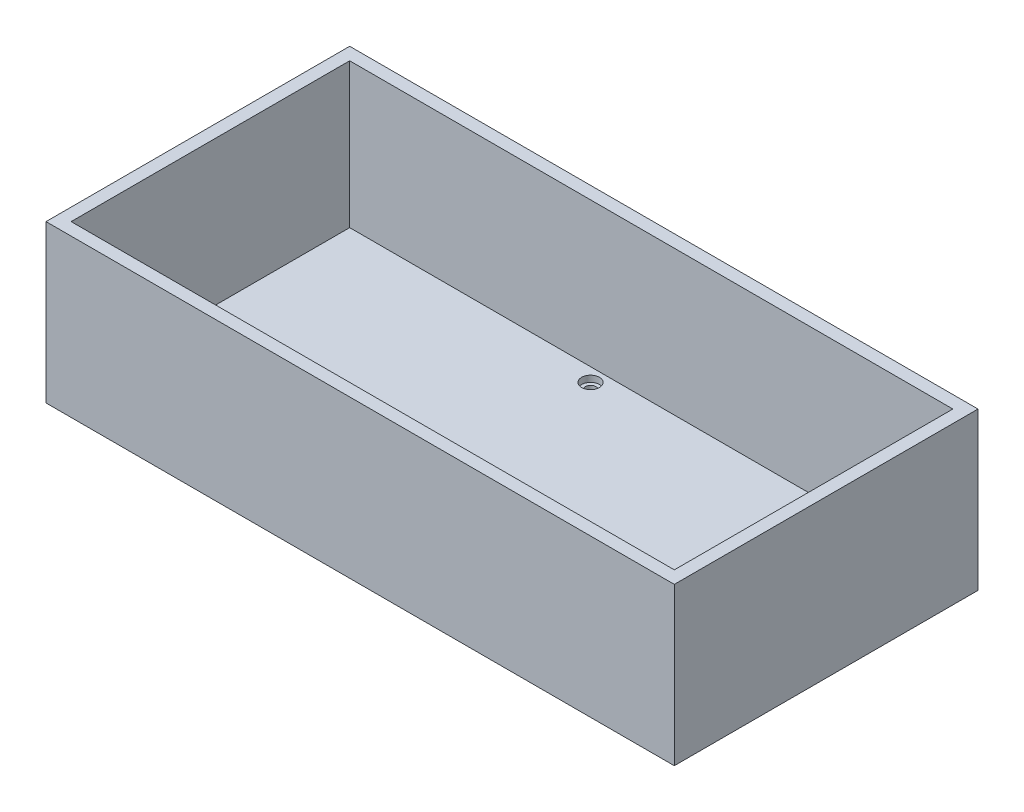
SolidWorks part; units mm, degrees
material "Polypropylene"
ref_plane "正面" through (0, 0, 0) normal (0, 0, 1) x (1, 0, 0)
ref_plane "平面" through (0, 0, 0) normal (0, 1, 0) x (1, 0, 0)
ref_plane "右側面" through (0, 0, 0) normal (1, 0, 0) x (0, 0, -1)
sketch "ｽｹｯﾁ1" plane through (0, 0, 0) normal (0, 1, 0) x (1, 0, 0)
  line L1 (-150, 72.5) -> (150, 72.5)
  line L2 (-150, 72.5) -> (-150, -72.5)
  line L3 (-150, -72.5) -> (150, -72.5)
  line L4 (150, 72.5) -> (150, -72.5)
  line L5 (-150, 72.5) -> (150, -72.5) construction
  line L6 (-150, -72.5) -> (150, 72.5) construction
  point P0 (0, 0)
  dimension "D1" = 300
  dimension "D2" = 145
extrude "ﾎﾞｽ - 押し出し1" add sketch "ｽｹｯﾁ1" along normal blind 75
shell "ｼｪﾙ1" thickness 6 removed face at (0, 75, 0)
sketch "ｽｹｯﾁ2" plane through (0, 6, 0) normal (0, 1, 0) x (1, 0, 0)
  line L0 (140, 72.5) -> (140, -72.5) construction
  line L1 (150, 72.5) -> (-150, 72.5) construction
  line L2 (-150, -72.5) -> (150, -72.5) construction
  line L3 (140, -72.5) -> (-22.5, -72.5) construction
  line L4 (-22.5, -72.5) -> (-22.5, 72.5) construction
  line L6 (150, -72.5) -> (150, 72.5) construction
  line L7 (-22.5, 0) -> (140, 0) construction
  line L8 (58.75, 72.5) -> (58.75, -72.5) construction
  circle A0 centre (140, 60) radius 2.55
  circle A1 centre (140, -60) radius 2.55
  circle A2 centre (-22.5, -60) radius 2.55
  circle A3 centre (-22.5, 60) radius 2.55
  point P18 (58.75, 0)
  dimension "D3" = 5.1
  dimension "D1" = 162.5
  dimension "D2" = 10
  dimension "D4" = 60
extrude "ｶｯﾄ - 押し出し1" cut sketch "ｽｹｯﾁ2" against normal through all
sketch "ｽｹｯﾁ3" plane through (0, 6, 0) normal (0, 1, 0) x (1, 0, 0)
  circle A0 centre (140, 60) radius 4.25
  circle A1 centre (-22.5, 60) radius 4.25
  circle A2 centre (-22.5, -60) radius 4.25
  circle A3 centre (140, -60) radius 4.25
  dimension "D1" = 8.5
extrude "ｶｯﾄ - 押し出し2" cut sketch "ｽｹｯﾁ3" against normal blind 3
